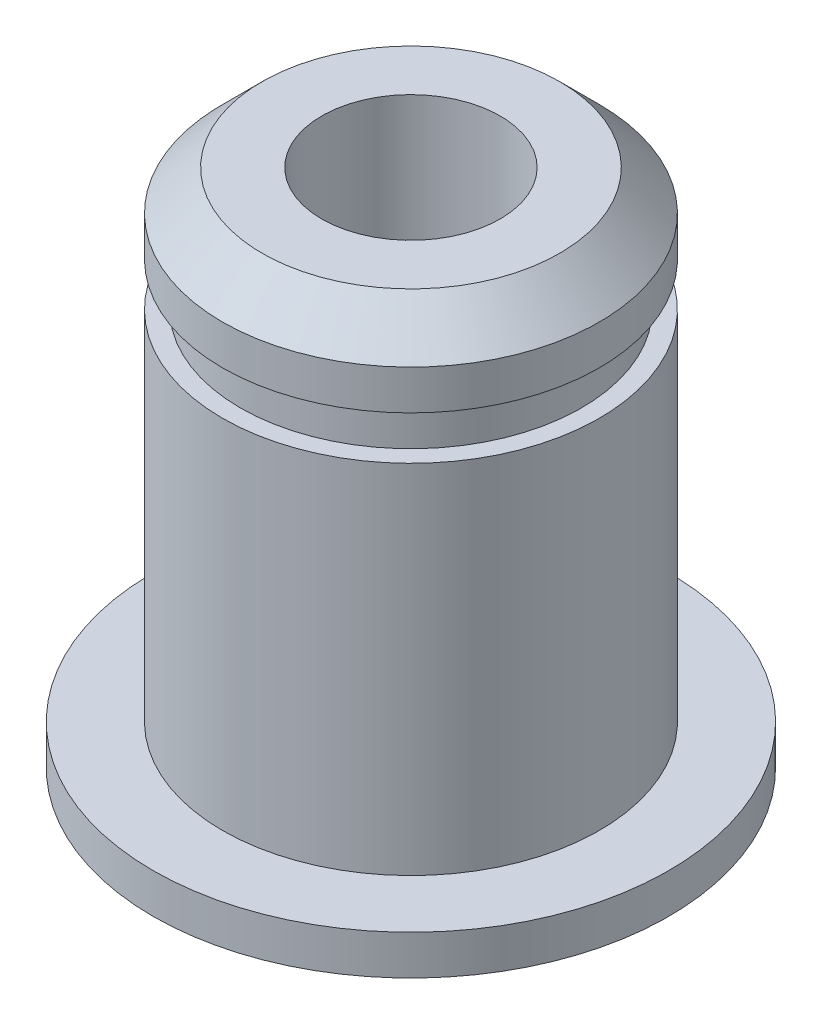
SolidWorks part; units mm, degrees
ref_plane "Front Plane" through (0, 0, 0) normal (0, 0, 1) x (1, 0, 0)
ref_plane "Top Plane" through (0, 0, 0) normal (0, 1, 0) x (1, 0, 0)
ref_plane "Right Plane" through (0, 0, 0) normal (1, 0, 0) x (0, 0, -1)
sketch "Sketch1" plane through (0, 0, 0) normal (0, 0, 1) x (1, 0, 0)
  line L0 (0, 0) -> (6.5, 0)
  line L1 (6.5, 0) -> (6.5, 1)
  line L2 (6.5, 1) -> (4.75, 1)
  line L3 (4.75, 1) -> (4.75, 10)
  line L4 (4.75, 10) -> (4.3, 10)
  line L5 (4.3, 10) -> (4.3, 11.1)
  line L6 (4.3, 11.1) -> (4.75, 11.1)
  line L7 (4.75, 11.1) -> (4.75, 13.1)
  line L8 (4.75, 13.1) -> (0, 13.1)
  line L9 (0, 13.1) -> (0, 0)
  line L10 (0, 22.9918) -> (0, -6.294) construction
  line L12 (0, 0) -> (2.25, 0)
  line L13 (0, 0) -> (0, 13.1)
  line L14 (0, 13.1) -> (2.25, 13.1)
  line L15 (2.25, 0) -> (2.25, 13.1)
  dimension "D1" = 6.5
  dimension "D2" = 4.3
  dimension "D3" = 1
  dimension "D4" = 9
  dimension "D5" = 2.5
  dimension "D6" = 1.1
  dimension "D7" = 2
  dimension "D8" = 6.5
  dimension "D9" = 4.75
revolve "Revolve1" add sketch "Sketch1" angle 360 about L9 region at (3.5944, 6.1804, 0)
chamfer "Chamfer1" distance 1 angle 45 1 edges at (0, 13.1, 4.75)
